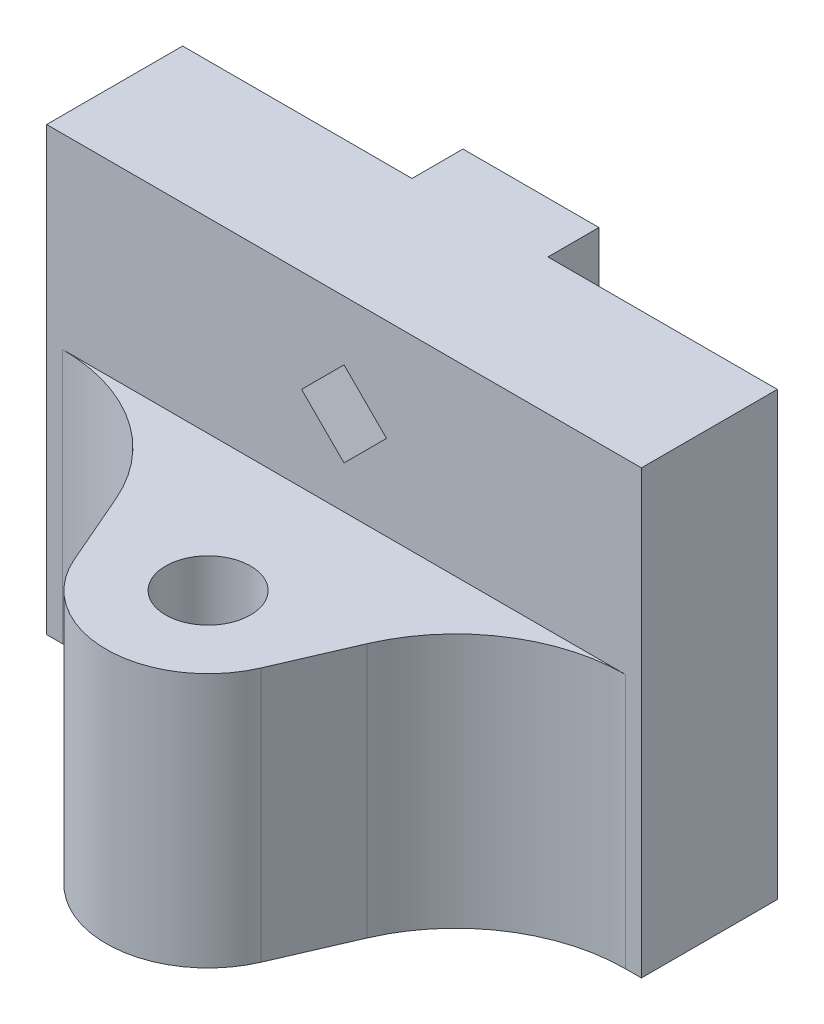
SolidWorks part; units mm, degrees
ref_plane "Ebene vorne" through (0, 0, 0) normal (0, 0, 1) x (1, 0, 0)
ref_plane "Ebene oben" through (0, 0, 0) normal (0, 1, 0) x (1, 0, 0)
ref_plane "Ebene rechts" through (0, 0, 0) normal (1, 0, 0) x (0, 0, -1)
sketch "Skizze1" plane through (0, 0, 0) normal (0, 0, 1) x (1, 0, 0)
  line L0 (0, 36.3792) -> (0, -29.748) construction
  line L1 (-27.82, 0) -> (18.1368, 0) construction
  line L2 (17.5, 6) -> (-17.5, 6)
  line L3 (-17.5, 6) -> (-17.5, -20)
  line L4 (-17.5, -20) -> (17.5, -20)
  line L5 (17.5, 6) -> (17.5, -20)
  line L6 (0, 2.5) -> (-2.5, 0)
  line L7 (-2.5, 0) -> (0, -2.5)
  line L8 (0, -2.5) -> (2.5, 0)
  line L9 (2.5, 0) -> (0, 2.5)
  circle A0 centre (0, 0) radius 2.5 construction
  circle A1 centre (0, 0) radius 4.5 construction
  point P11 (0, -20)
  point P12 (0, 6)
  dimension "D4" = 5
  dimension "D5" = 9
  dimension "D1" = 35
  dimension "D2" = 6
  dimension "D3" = 20
extrude "Aufsatz-Linear austragen1" add sketch "Skizze1" along normal blind 8
sketch "Skizze2" plane through (0, 0, 0) normal (0, 0, -1) x (-1, 0, 0)
  line L0 (0, 26.2767) -> (0, -51.1728) construction
  line L1 (-25.1244, 0) -> (26.6334, 0) construction
  line L2 (-17.5, 6) -> (17.5, 6) construction
  line L3 (17.5, -20) -> (-17.5, -20) construction
  line L5 (0, 6) -> (-4, 6)
  line L6 (-4, 6) -> (-4, -20)
  line L7 (-4, -20) -> (0, -20)
  line L8 (4, -20) -> (0, -20)
  line L9 (4, 6) -> (4, -20)
  line L10 (0, 6) -> (4, 6)
  line L18 (-2.5, 0) -> (0, -2.5)
  line L19 (0, -2.5) -> (2.5, 0)
  line L20 (2.5, 0) -> (0, 2.5)
  line L21 (0, 2.5) -> (-2.5, 0)
  line L22 (-2.5, 0) -> (0, -2.5)
  line L23 (0, -2.5) -> (2.5, 0)
  line L24 (2.5, 0) -> (0, 2.5)
  line L25 (0, 2.5) -> (-2.5, 0)
  dimension "D1" = 8
  dimension "D2" = 0
extrude "Aufsatz-Linear austragen2" add sketch "Skizze2" along normal blind 3
sketch "Skizze3" plane through (0, -20, 0) normal (0, -1, 0) x (1, 0, 0)
  line L0 (0, 29.3144) -> (0, -13.3144) construction
  line L1 (-27.7823, 0) -> (35.6297, 0) construction
  line L2 (0, 8) -> (-10, 8)
  line L3 (-10, 8) -> (-5.5065, 18.3831)
  line L4 (0, 8) -> (10, 8)
  line L5 (10, 8) -> (5.5065, 18.3831)
  line L6 (-17.5, 8) -> (17.5, 8) construction
  arc A0 (-5.5065, 18.3831) -> (5.5065, 18.3831) centre (0, 16) cw
  circle A1 centre (0, 16) radius 2.5
  dimension "D1" = 5
  dimension "D4" = 6
  dimension "D2" = 8
  dimension "D3" = 20
extrude "Aufsatz-Linear austragen3" add sketch "Skizze3" against normal blind 15
ref_axis "Achse1" through (0, -5, 16) along (0, -1, 0)
fillet "Verrundung1" radius 10 2 edges
